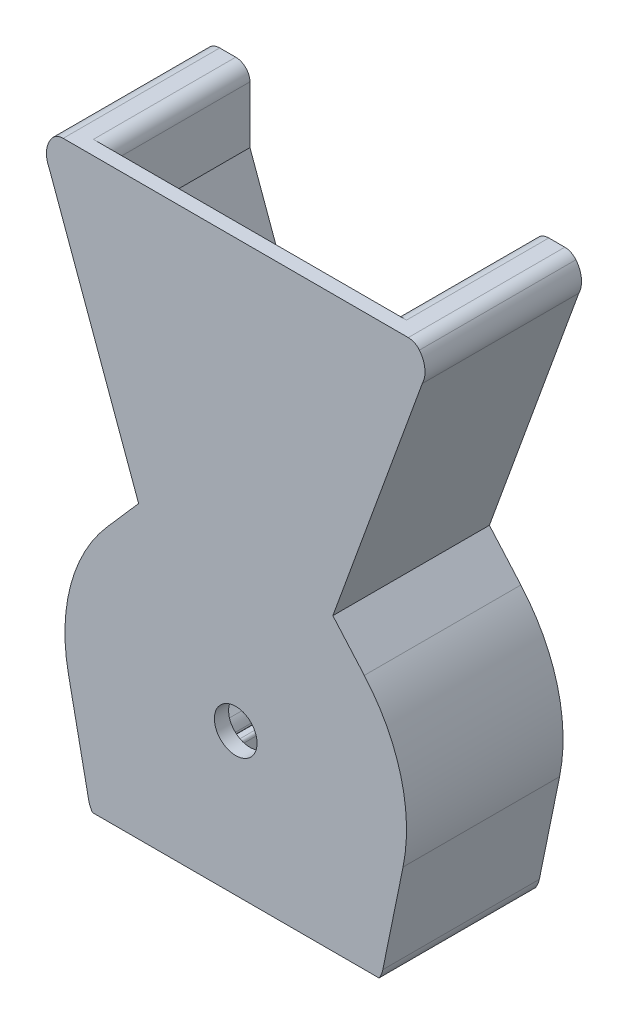
SolidWorks part; units mm, degrees
ref_plane "Front Plane" through (0, 0, 0) normal (0, 0, 1) x (1, 0, 0)
ref_plane "Top Plane" through (0, 0, 0) normal (0, 1, 0) x (1, 0, 0)
ref_plane "Right Plane" through (0, 0, 0) normal (1, 0, 0) x (0, 0, -1)
sketch "Boundaries" plane through (0, 0, 0) normal (0, 0, 1) x (1, 0, 0)
  line L1 (-80, 100) -> (80, 100) construction
  line L2 (-80, 100) -> (-80, -100) construction
  line L3 (-80, -100) -> (80, -100) construction
  line L4 (80, 100) -> (80, -100) construction
  point P0 (0, 0)
  point P7 (0, 100)
  point P8 (80, 0)
  dimension "D1" = 160
  dimension "D2" = 200
sketch "Sketch2" plane through (0, 0, 0) normal (0, 0, 1) x (1, 0, 0)
  line L0 (-80, -100) -> (80, -100) construction
  line L1 (-53.1957, 0) -> (53.1957, 0) construction
  line L4 (-50, 75) -> (50, 75) construction
  line L5 (-50, 75) -> (-22.7022, 0)
  line L6 (50, 75) -> (22.7022, 0)
  line L7 (-53.1957, 0) -> (-22.7022, 0) construction
  line L8 (-80, 100) -> (-50, 100)
  line L9 (-80, 100) -> (-80, -100)
  line L10 (-80, -100) -> (-35.3553, -100)
  line L11 (80, 100) -> (80, -100)
  line L12 (22.7022, 0) -> (53.1957, 0) construction
  line L13 (-50, 75) -> (-50, 100)
  line L14 (50, 75) -> (50, 100)
  line L15 (50, 100) -> (80, 100)
  line L16 (-37.6439, -17.092) -> (-22.7022, 0)
  line L17 (22.7022, 0) -> (37.6439, -17.092)
  line L20 (35.3553, -100) -> (80, -100)
  line L21 (-35.3553, -100) -> (35.3553, -100) construction
  line L22 (-35.3553, -14.6447) -> (35.3553, -85.3553) construction
  line L23 (-35.3553, -85.3553) -> (35.3553, -14.6447) construction
  line L24 (0, 0) -> (0, -50) construction
  line L26 (-35.3553, -100) -> (-35.3553, -85.3553)
  line L27 (35.3553, -100) -> (35.3553, -85.3553)
  arc A0 (-37.6439, -17.092) -> (-35.3553, -85.3553) centre (0, -50) ccw construction
  arc A1 (-37.6439, -17.092) -> (-35.3553, -85.3553) centre (0, -50) ccw
  arc A2 (35.3553, -85.3553) -> (37.6439, -17.092) centre (0, -50) ccw construction
  arc A3 (35.3553, -85.3553) -> (37.6439, -17.092) centre (0, -50) ccw
  circle A4 centre (0, -50) radius 50 construction
  point P12 (0, 0)
  point P13 (0, 75)
  point P26 (0, -100)
  point P31 (0, -50)
  point P34 (0, -50)
  dimension "D1" = 100
  dimension "D2" = 45
  dimension "D3" = 45
  dimension "D4" = 70
  dimension "D5" = 70
  dimension "D8" = 100
  dimension "D9" = 75
  dimension "D10" = 45.4045
extrude "Boss-Extrude1" add sketch "Sketch2" against normal blind 50
sketch "Sketch3" plane through (0, 0, 0) normal (0, 0, 1) x (1, 0, 0)
  line L0 (-29.9816, 20) -> (29.9816, 20)
  line L1 (-50, 75) -> (-22.7022, 0) construction
  line L2 (50, 75) -> (22.7022, 0) construction
  line L3 (29.9816, 20) -> (22.7022, 0)
  line L4 (22.7022, 0) -> (-22.7022, 0)
  line L5 (-22.7022, 0) -> (-29.9816, 20)
  dimension "D1" = 20
extrude "Boss-Extrude2" add sketch "Sketch3" against normal blind 10
chamfer "Chamfer1" distance 20 distance2 15 1 edges at (0, 20, -10) first distance on face at (0, 10, -10)
sketch "Sketch4" plane through (0, 0, 0) normal (0, 0, 1) x (1, 0, 0)
  line L1 (-80, 100) -> (80, 100)
  line L2 (-80, 100) -> (-80, -100)
  line L3 (-80, -100) -> (80, -100)
  line L4 (80, 100) -> (80, -100)
extrude "Boss-Extrude3" add sketch "Sketch4" along normal blind 5
fillet "Fillet1" radius 10 5 edges at (-35.3553, -85.3553, -25) (-22.7022, 0, -30) (22.7022, 0, -30) (0, 13.3333, 0) (35.3553, -85.3553, -25)
sketch "Sketch5" plane through (0, 0, 0) normal (0, 0, -1) x (-1, 0, 0)
  circle A0 centre (0, -50) radius 7.5
  dimension "D1" = 15
extrude "Cut-Extrude1" cut sketch "Sketch5" against normal up to surface (5 mm away) up to face at (0, 0, 5)
sketch "Sketch11" plane through (0, 0, -50) normal (0, 0, -1) x (-1, 0, 0)
  line L0 (80, -100) -> (-80, -100) construction
  line L1 (-35.3553, -100) -> (-35.3553, -85.3553) construction
  line L2 (-58.7842, -62.0174) -> (-51.673, -96.8026)
  line L3 (-80, -100) -> (-50.3387, -100)
  line L4 (0, -100) -> (0, 100) construction
  line L5 (34.1202, 2.1327) -> (45.1727, -10.5104)
  line L6 (60, 73.2367) -> (34.1202, 2.1327)
  line L7 (60, 73.2367) -> (65.537, 88.4494)
  line L8 (80, 100) -> (-80, 100) construction
  line L9 (-50, 75) -> (-50, 100) construction
  line L10 (-60, 73.2367) -> (-65.537, 88.4494)
  line L11 (-80, 100) -> (-80, -100) construction
  line L12 (-45.3553, -89.2797) -> (-45.3553, -100)
  line L13 (-34.1202, 2.1327) -> (-45.1727, -10.5104)
  line L14 (-60, 73.2367) -> (-34.1202, 2.1327)
  line L15 (-60, 100) -> (-60, 73.2367)
  line L17 (-34.1202, 2.1327) -> (-45.1727, -10.5104)
  line L18 (-60, 73.2367) -> (-34.1202, 2.1327)
  line L19 (-80, 100) -> (-80, -100)
  line L20 (-62.4749, 100) -> (-80, 100)
  line L21 (62.4749, 100) -> (80, 100)
  line L22 (80, 100) -> (80, -100)
  line L23 (80, -100) -> (50.3387, -100)
  line L24 (58.7842, -62.0174) -> (51.673, -96.8026)
  circle A0 centre (-42.8553, -95) radius 1.5 construction
  arc A1 (-51.673, -96.8026) -> (-50.3387, -100) centre (-42.8553, -95) ccw
  arc A2 (62.4749, 100) -> (65.537, 88.4494) centre (57.5, 92.5) cw
  arc A3 (51.673, -96.8026) -> (50.3387, -100) centre (42.8553, -95) cw
  arc A4 (45.1727, -10.5104) -> (58.7842, -62.0174) centre (0, -50) cw
  circle A6 centre (-57.5, 92.5) radius 1.5 construction
  arc A7 (-62.4749, 100) -> (-65.537, 88.4494) centre (-57.5, 92.5) ccw
  arc A9 (-45.1727, -10.5104) -> (-45.3553, -89.2797) centre (0, -50) ccw
  arc A10 (-45.1727, -10.5104) -> (-58.7842, -62.0174) centre (0, -50) ccw
  dimension "D3" = 3
  dimension "D4" = 7.5
  dimension "D5" = 7.5
  dimension "D7" = 7.5
  dimension "D8" = 7.5
  dimension "D2" = 7.5
  dimension "D6" = 5
  dimension "D1" = 10
extrude "Cut-Extrude5" cut sketch "Sketch11" against normal through all and the other way through all
fillet "Fillet4" radius 5 6 edges at (-50, 100, -25) (50, 100, -25) (-35.3553, -100, -25) (35.3553, -100, -25) (-62.4749, 100, -22.5) (62.4749, 100, -22.5)
ref_plane "MidPlane" through (0, 0, -25) normal (0, 0, -1) x (-1, 0, 0)
ref_axis "Food Drop Axis" through (0, 124.9402, -25) along (0, -1, 0)
sketch "Sketch12" plane through (0, 0, -50) normal (0, 0, -1) x (-1, 0, 0)
  circle A0 centre (-57.5, 92.5) radius 2
  circle A1 centre (57.5, 92.5) radius 2
  circle A2 centre (-42.8553, -95) radius 2
  circle A3 centre (42.8553, -95) radius 2
  dimension "D1" = 4
extrude "Cut-Extrude6" cut sketch "Sketch12" against normal blind 10
sketch "Sketch13" plane through (0, 0, -50) normal (0, 0, -1) x (-1, 0, 0)
  line L0 (-35.3553, -89.2797) -> (-35.3553, -95) construction
  line L1 (-45.3553, -87.6922) -> (-22.8553, -87.6922) construction
  line L2 (-45.3553, -87.6922) -> (-45.3553, -89.2797) construction
  line L3 (-45.3553, -89.2797) -> (-22.8553, -89.2797) construction
  line L4 (-22.8553, -87.6922) -> (-22.8553, -89.2797) construction
  line L5 (-45.5553, -87.4922) -> (-22.6553, -87.4922)
  line L6 (-22.6553, -87.4922) -> (-22.6553, -89.4797)
  line L7 (-45.5553, -89.4797) -> (-22.6553, -89.4797)
  line L8 (-45.5553, -87.4922) -> (-45.5553, -89.4797)
  line L9 (0, -100) -> (0, -49.363) construction
  line L10 (40.3553, -100) -> (-40.3553, -100) construction
  line L11 (45.5553, -87.4922) -> (45.5553, -89.4797)
  line L12 (45.5553, -89.4797) -> (22.6553, -89.4797)
  line L13 (22.6553, -87.4922) -> (22.6553, -89.4797)
  line L14 (45.5553, -87.4922) -> (22.6553, -87.4922)
  dimension "D1" = 1.5875
  dimension "D2" = 10
  dimension "D3" = 12.5
  dimension "D4" = 0.2
extrude "Cut-Extrude7" cut sketch "Sketch13" against normal up to surface (50 mm away) up to face at (-7.5, -50, 0)
fillet "Fillet5" radius 1 4 edges at (-35.3553, -89.4797, -25) (-35.5164, -87.4922, -25) (35.3553, -89.4797, -25) (35.5164, -87.4922, -25)
